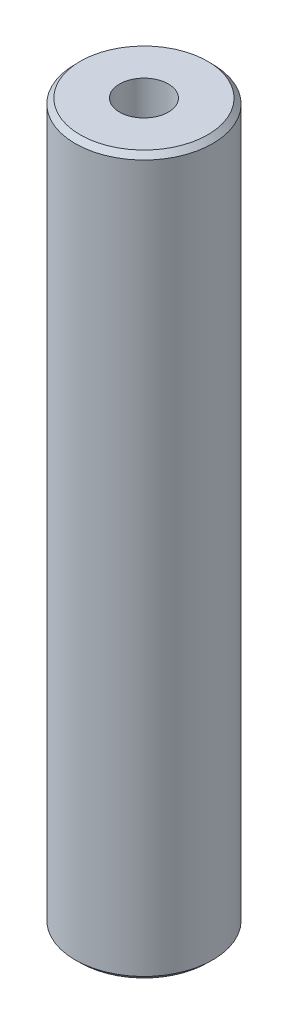
SolidWorks part; units mm, degrees
ref_plane "Front Plane" through (0, 0, 0) normal (0, 0, 1) x (1, 0, 0)
ref_plane "Top Plane" through (0, 0, 0) normal (0, 1, 0) x (1, 0, 0)
ref_plane "Right Plane" through (0, 0, 0) normal (1, 0, 0) x (0, 0, -1)
sketch "Sketch1" plane through (0, 0, 0) normal (0, 1, 0) x (1, 0, 0)
  circle A0 centre (0, 0) radius 57.5
  dimension "SHAFT_OD" = 115
extrude "Boss-Extrude1" add sketch "Sketch1" along normal blind 600
sketch "Sketch2" plane through (0, 0, 0) normal (0, 1, 0) x (1, 0, 0)
  circle A0 centre (0, 0) radius 20.4308
  dimension "BORE_D" = 40.8615
extrude "Cut-Extrude1" cut sketch "Sketch2" along normal through all
chamfer "Chamfer1" distance 4.2879 angle 44.187 2 edges at (0, 600, 57.5) (0, 0, 57.5) first distance on face at (0, 600, 57.5) first distance on face at (0, 0, 20.4308)
